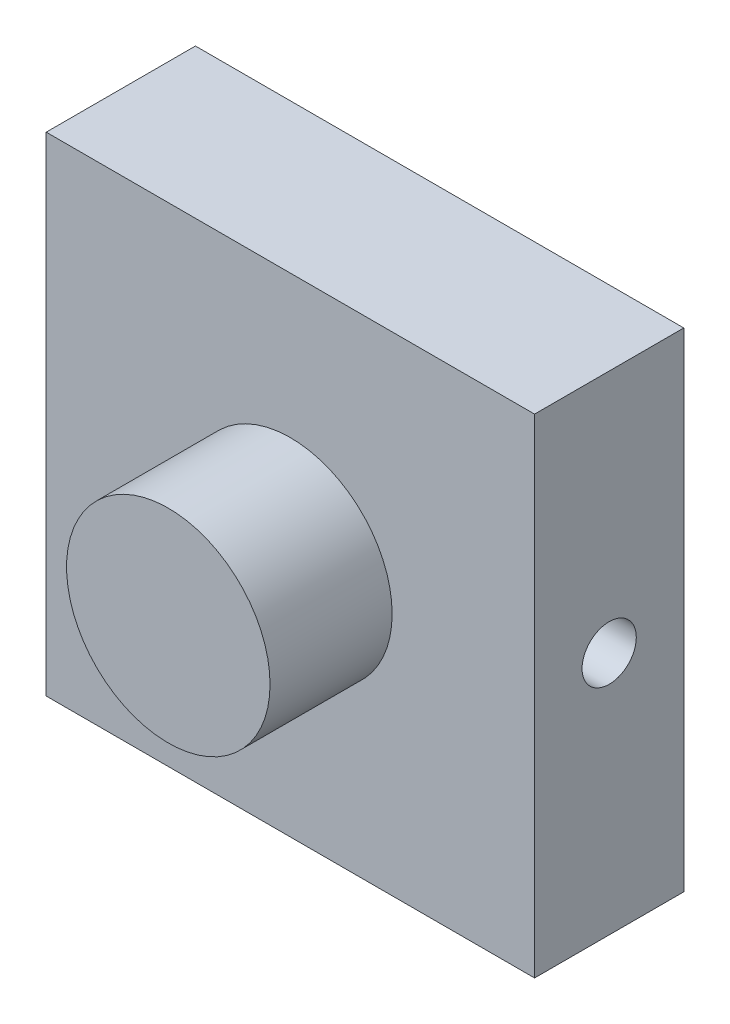
SolidWorks part; units mm, degrees
material "AISI 4130 钢，正火温度为 870C"
ref_plane "前视基准面" through (0, 0, 0) normal (0, 0, 1) x (1, 0, 0)
ref_plane "上视基准面" through (0, 0, 0) normal (0, 1, 0) x (1, 0, 0)
ref_plane "右视基准面" through (0, 0, 0) normal (1, 0, 0) x (0, 0, -1)
other "Configuration Table"
sketch "草图1" plane through (0, 0, 0) normal (0, 0, 1) x (1, 0, 0)
  line L0 (36, 18) -> (18, 18) construction
  line L1 (0, 0) -> (36, 0)
  line L2 (0, 0) -> (0, 36)
  line L3 (0, 36) -> (36, 36)
  line L4 (36, 0) -> (36, 36)
  line L5 (18, 18) -> (18, 36) construction
  circle A0 centre (18, 18) radius 7.5
  dimension "D3" = 15
  dimension "D1" = 36
  dimension "D2" = 36
extrude "凸台-拉伸1" add sketch "草图1" along normal blind 11 contours A0 | L1 L4 L3 L2 A0 region at (0.5091, 18, 0) region at (18, 18, 0)
extrude "凸台-拉伸2" add sketch "草图1<3>" along normal blind 9 from surface contours A0 region at (18, 18, 0) starting at face at (18, 18, 11)
sketch "草图1<3>" plane through (0, 0, 0) normal (0, 0, 1) x (1, 0, 0) same geometry as "草图1"
sketch "草图2" plane through (36, 0, 0) normal (1, 0, 0) x (0, 0, -1)
  line L0 (0, 0) -> (0, 36) construction
  line L1 (-5.5, 18) -> (0, 18) construction
  circle A0 centre (-5.5, 18) radius 2
  dimension "D1" = 4
  dimension "D2" = 5.5
extrude "切除-拉伸1" cut sketch "草图2" against normal blind 3
extrude "切除-拉伸2" cut sketch "草图2<2>" along normal blind 3 from surface starting at face at (0, 18, 5.5)
sketch "草图2<2>" plane through (36, 0, 0) normal (1, 0, 0) x (0, 0, -1) same geometry as "草图2"
